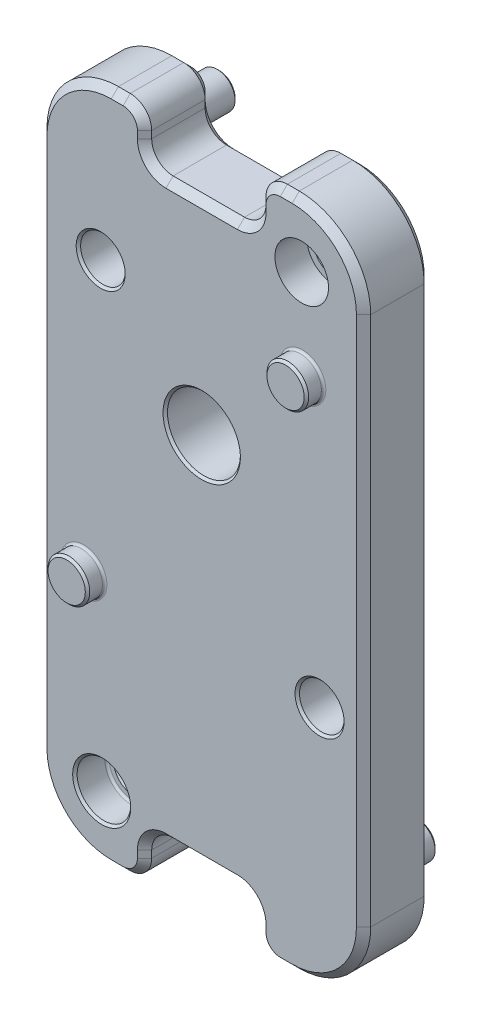
SolidWorks part; units mm, degrees
ref_plane "Front" through (0, 0, 0) normal (0, 0, 1) x (1, 0, 0)
ref_plane "Top" through (0, 0, 0) normal (0, 1, 0) x (1, 0, 0)
ref_plane "Right" through (0, 0, 0) normal (1, 0, 0) x (0, 0, -1)
sketch "Sketch2" plane through (0, 0, 0) normal (0, 0, 1) x (1, 0, 0)
  line L0 (0, 15.3416) -> (0, -37.3507) construction
  line L1 (14.3891, -37.3507) -> (-14.3891, -37.3507)
  line L2 (14.3891, -37.3507) -> (14.3891, 22.4818)
  line L4 (-14.3891, -37.3507) -> (-14.3891, 22.4818)
  line L5 (-15.4933, 0) -> (15.4933, 0) construction
  line L6 (-14.3891, 15.3416) -> (14.3891, 15.3416) construction
  line L7 (-14.3891, 22.4818) -> (14.3891, 22.4818)
  line L8 (-14.3891, -28.0416) -> (14.3891, -28.0416) construction
  line L9 (-14.3891, -31.8516) -> (14.3891, -31.8516) construction
  line L10 (-8.89, 16.9827) -> (-8.89, -31.8516) construction
  line L11 (8.89, 16.9827) -> (8.89, -31.8516) construction
  circle A1 centre (0, 0) radius 3.2385
  arc A2 (-15.4933, 0) -> (15.4933, 0) centre (0, -0.1524) cw construction
  arc A3 (-19.3034, 0) -> (19.3034, 0) centre (0, -0.1524) cw construction
  circle A5 centre (8.89, 16.9827) radius 1.5875
  circle A6 centre (-8.89, -31.8516) radius 1.5875
  point P10 (0, 0)
  dimension "D3" = 15.3416
  dimension "D2" = 15.494
  dimension "D4" = 6.477
  dimension "D6" = 3.81
  dimension "D7" = 3.175
  dimension "D10" = 5.4991
  dimension "D1" = 28.7782
  dimension "D5" = 43.3832
  dimension "D8" = 5.4991
  dimension "D9" = 5.4991
  dimension "D11" = 3.81
  dimension "D12" = 5.4991
extrude "Boss-Extrude1" add sketch "Sketch2" along normal blind 6.0198
sketch "Sketch3" plane through (0, 0, 6.0198) normal (0, 0, 1) x (1, 0, 0)
  circle A0 centre (-8.89, -31.8516) radius 2.3813
  circle A2 centre (8.89, 16.9827) radius 2.3812
  dimension "D1" = 4.7625
extrude "Cut-Extrude1_Counter-sink" cut sketch "Sketch3" against normal blind 2.8448
sketch "Sketch4" plane through (0, 0, 0) normal (0, 0, -1) x (-1, 0, 0)
  line L11 (-8.89, 16.9827) -> (8.89, 16.9827) construction
  line L12 (-8.89, 16.9827) -> (-8.89, -31.8516) construction
  line L13 (-8.89, -31.8516) -> (8.89, -31.8516) construction
  line L14 (8.89, 16.9827) -> (8.89, -31.8516) construction
  circle A0 centre (-8.89, -31.8516) radius 1.5875
  circle A1 centre (8.89, 16.9827) radius 1.5875
  circle A2 centre (-8.89, 16.9827) radius 1.5875 construction
  point P5 (10.5129, 17.3143)
  point P6 (9.0535, 16.9827)
  point P8 (-8.7708, -31.6553)
extrude "Boss-Extrude2_BackPegs" add sketch "Sketch4" along normal blind 4.445
sketch "Sketch5" plane through (0, 0, 6.0198) normal (0, 0, 1) x (1, 0, 0)
  line L0 (-10.4775, 22.4818) -> (-10.4775, -37.3507) construction
  line L1 (14.3891, 22.4818) -> (-14.3891, 22.4818) construction
  line L2 (-14.3891, -37.3507) -> (14.3891, -37.3507) construction
  line L3 (10.4775, 22.4818) -> (10.4775, -37.3507) construction
  line L4 (-10.4775, -7.4344) -> (10.4775, -7.4344) construction
  line L5 (0, 0) -> (0, -7.4344) construction
  line L6 (-14.3891, 22.4818) -> (-14.3891, -37.3507) construction
  circle A0 centre (-10.4775, -15.748) radius 1.9812 construction
  circle A1 centre (10.4775, -15.748) radius 1.9812
  circle A2 centre (0, 0) radius 12.7 construction
  circle A3 centre (-8.9789, 8.9816) radius 1.9812
  circle A4 centre (8.9789, 8.9816) radius 1.9812 construction
  dimension "D2" = 3.9624
  dimension "D3" = 25.4
  dimension "D1" = 20.955
  dimension "D4" = 5.4102
  dimension "D5" = 15.748
extrude "Cut-Extrude2_EncoderScrewHoles" cut sketch "Sketch5" against normal through all
sketch "Sketch6" plane through (0, 0, 6.0198) normal (0, 0, 1) x (1, 0, 0)
  line L0 (-10.4775, 22.4818) -> (-10.4775, -37.3507) construction
  line L1 (10.4775, 22.4818) -> (10.4775, -37.3507) construction
  line L2 (-10.4775, -7.4344) -> (10.4775, -7.4344) construction
  line L3 (0, 0) -> (0, -7.4344) construction
  line L4 (14.3891, 22.4818) -> (-14.3891, 22.4818) construction
  line L5 (-14.3891, -37.3507) -> (14.3891, -37.3507) construction
  line L6 (-14.3891, 22.4818) -> (-14.3891, -37.3507) construction
  circle A0 centre (-10.4775, -15.748) radius 1.8542
  circle A1 centre (10.4775, -15.748) radius 1.8542 construction
  circle A2 centre (0, 0) radius 12.7 construction
  circle A3 centre (-8.9789, 8.9816) radius 1.8542 construction
  circle A4 centre (8.9789, 8.9816) radius 1.8542
  dimension "D2" = 3.7084
  dimension "D3" = 25.4
  dimension "D1" = 20.955
  dimension "D4" = 15.748
  dimension "D5" = 5.4102
extrude "Boss-Extrude3_EncoderPegs" add sketch "Sketch6" along normal blind 1.524
ref_axis "Axis1" through (0, 0, 36.0066) along (0, 0, -1)
ref_plane "Plane1" through (0, 0, 0) normal (0, 1, 0) x (1, 0, 0)
sketch "Sketch8" plane through (0, 0, 0) normal (0, 1, 0) x (1, 0, 0)
  line L0 (0, 7.9624) -> (0, -6.0198) construction
  line L1 (-14.3891, -6.0198) -> (14.3891, -6.0198) construction
  line L2 (-2.3812, 0) -> (-2.3812, 3.175)
  line L3 (-14.3891, 0) -> (14.3891, 0) construction
  line L4 (-2.3812, 3.175) -> (-3.9687, 3.175)
  line L5 (-3.9687, 3.175) -> (-3.9687, 0.1984)
  line L6 (-2.3812, 0) -> (-4.1672, 0)
  arc A0 (-3.9687, 0.1984) -> (-4.1672, 0) centre (-4.1672, 0.1984) cw
  dimension "D1" = 0.1984
  dimension "D2" = 3.175
  dimension "D3" = 1.5875
  dimension "D4" = 2.3813
revolve "Revolve1" [suppressed] add sketch "Sketch8" angle 360 about L0
sketch "Sketch7" plane through (0, 0, 0) normal (0, 0, -1) x (-1, 0, 0)
  line L0 (0, 22.4818) -> (0, -37.3507) construction
  line L1 (-14.3891, 22.4818) -> (14.3891, 22.4818) construction
  line L2 (14.3891, -37.3507) -> (-14.3891, -37.3507) construction
  line L3 (-14.3891, -11.9507) -> (14.3891, -11.9507) construction
  circle A0 centre (0, -11.9507) radius 3.9688
  dimension "D1" = 7.9375
  dimension "D2" = 25.4
extrude "Boss-Extrude4" add sketch "Sketch7" along normal blind 3.175
sketch "Sketch10" plane through (0, 0, 0) normal (0, 0, -1) x (-1, 0, 0)
  line L0 (-8.89, 16.9827) -> (-8.89, -37.3507) construction
  line L1 (-14.3891, 22.4818) -> (14.3891, 22.4818) construction
  line L2 (14.3891, -37.3507) -> (-14.3891, -37.3507) construction
  line L3 (0, 22.4818) -> (0, -37.3507) construction
  line L4 (-8.89, 16.9827) -> (-8.89, 22.4818) construction
  line L6 (-5.08, 22.4818) -> (5.08, 22.4818)
  line L7 (-5.08, 22.4818) -> (-5.08, 18.0368)
  line L8 (-5.08, 18.0368) -> (5.08, 18.0368)
  line L9 (5.08, 22.4818) -> (5.08, 18.0368)
  point P15 (0, 18.0368)
  dimension "D1" = 4.445
  dimension "D2" = 3.81
extrude "Cut-Extrude3" cut sketch "Sketch10" against normal through all
ref_plane "Midplane" through (0, -7.4344, 0) normal (0, -1, 0) x (-1, 0, 0)
mirror "Mirror1" about plane through (0, -7.4344, 0) normal (0, -1, 0) of "Cut-Extrude3"
fillet "Fillet1_0.25" radius 6.35 4 edges at (-14.3891, -37.3507, 3.0099) (14.3891, -37.3507, 3.0099) (14.3891, 22.4818, 3.0099) (-14.3891, 22.4818, 3.0099)
fillet "Fillet5" radius 1.905 4 edges at (-5.08, 22.4818, 3.0099) (5.08, 22.4818, 3.0099) (5.08, -37.3507, 3.0099) (-5.08, -37.3507, 3.0099)
fillet "Fillet4_0.075" radius 1.905 4 edges at (-5.08, 18.0368, 3.0099) (5.08, 18.0368, 3.0099) (-5.08, -32.9057, 3.0099) (5.08, -32.9057, 3.0099)
fillet "Fillet3_1/128" radius 0.1984 6 edges at (-6.5088, -31.8516, 3.175) (7.3025, -31.8516, 0) (-10.4775, 16.9827, 0) (7.1247, 8.9816, 6.0198) (-12.3317, -15.748, 6.0198) (-3.9688, -11.9507, 0)
chamfer "Chamfer1_0.25" distance 0.635 angle 45 22 edges at (-12.5292, -35.4908, 6.0198) (-14.3891, -7.4344, 6.0198) (-12.5292, 20.6219, 6.0198) (-12.5292, -35.4908, 0) (-14.3891, -7.4344, 0) (-12.5292, 20.6219, 0) (-7.512, 22.4818, 0) (-7.512, 22.4818, 6.0198) (5.08, 20.2593, 0) (4.522, 18.5948, 0) (0, 18.0368, 0) (-4.522, 18.5948, 0) (-5.08, 20.2593, 0) (5.08, 20.2593, 6.0198) (4.522, 18.5948, 6.0198) (0, 18.0368, 6.0198) (-4.522, 18.5948, 6.0198) (-5.08, 20.2593, 6.0198) (5.638, 21.9239, 0) (-5.638, 21.9239, 0) (5.638, 21.9239, 6.0198) (-5.638, 21.9239, 6.0198)
chamfer "Chamfer2_1/128" distance 0.1984 angle 45 14 edges at (-7.3025, -31.8516, 3.175) (3.2385, 0, 6.0198) (10.4775, 16.9827, 0) (-6.9977, 8.9816, 6.0198) (-10.9601, 8.9816, 0) (12.4587, -15.748, 6.0198) (8.4963, -15.748, 0) (7.3025, -31.8516, -4.445) (-10.4775, 16.9827, -4.445) (-8.6233, -15.748, 7.5438) (10.8331, 8.9816, 7.5438) (-7.3025, -31.8516, 0) (-6.5088, -31.8516, 6.0198) (10.4775, 16.9827, 3.175)
chamfer "Chamfer3_1/64" distance 0.3969 angle 45 1 edges at (-3.9688, -11.9507, -3.175)
